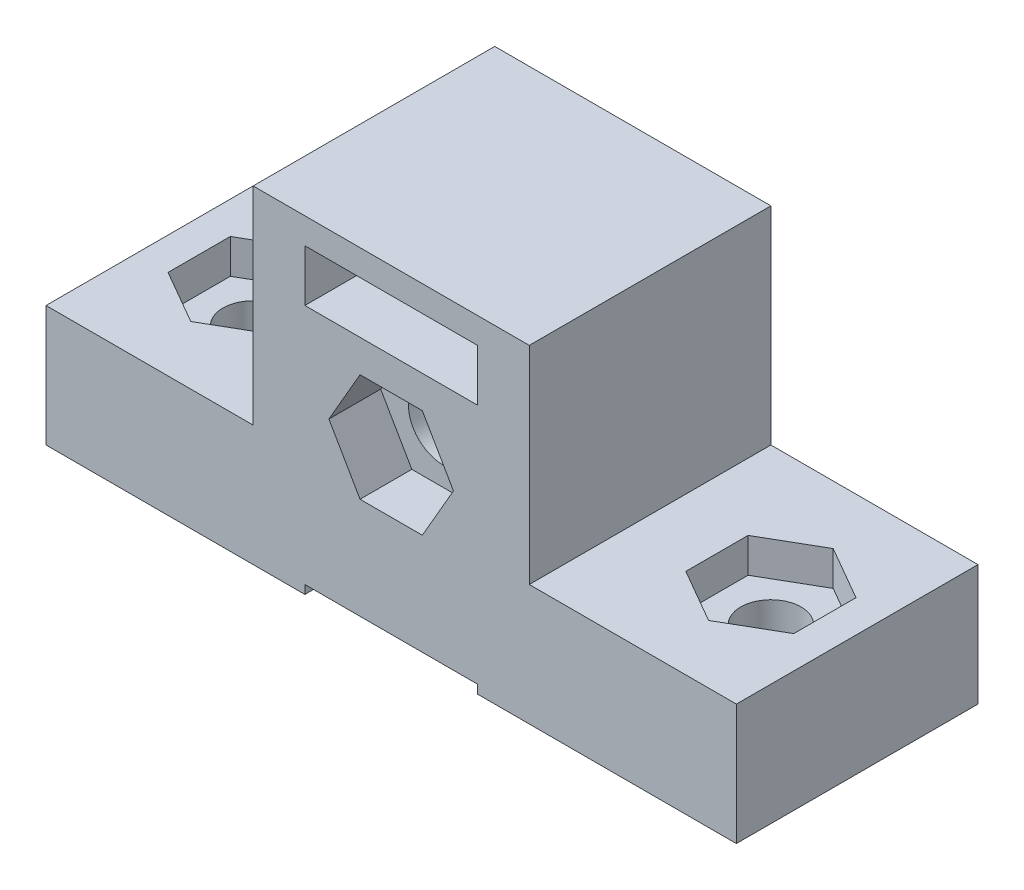
SolidWorks part; units mm, degrees
ref_plane "Front Plane" through (0, 0, 0) normal (0, 0, 1) x (1, 0, 0)
ref_plane "Top Plane" through (0, 0, 0) normal (0, 1, 0) x (1, 0, 0)
ref_plane "Right Plane" through (0, 0, 0) normal (1, 0, 0) x (0, 0, -1)
sketch "Sketch1" plane through (0, 0, 0) normal (0, 1, 0) x (1, 0, 0)
  line L1 (-20, 7) -> (20, 7)
  line L2 (-20, 7) -> (-20, -7)
  line L3 (-20, -7) -> (20, -7)
  line L4 (20, 7) -> (20, -7)
  line L5 (-20, 7) -> (20, -7) construction
  line L6 (-20, -7) -> (20, 7) construction
  point P0 (0, 0)
  dimension "D1" = 40
  dimension "D2" = 14
extrude "Boss-Extrude1" add sketch "Sketch1" along normal blind 19
sketch "Sketch2" plane through (0, 0, 7) normal (0, 0, 1) x (1, 0, 0)
  line L0 (0, 19) -> (0, 0) construction
  line L1 (-20, 19) -> (20, 19) construction
  line L3 (-5, 14.5) -> (5, 14.5)
  line L4 (-5, 14.5) -> (-5, 17.5)
  line L5 (-5, 17.5) -> (5, 17.5)
  line L6 (5, 14.5) -> (5, 17.5)
  line L7 (-5, 14.5) -> (5, 17.5) construction
  line L8 (-5, 17.5) -> (5, 14.5) construction
  line L9 (-5, -0.5) -> (5, -0.5)
  line L10 (-5, -0.5) -> (-5, 0.5)
  line L11 (-5, 0.5) -> (5, 0.5)
  line L12 (5, -0.5) -> (5, 0.5)
  line L13 (-5, -0.5) -> (5, 0.5) construction
  line L14 (-5, 0.5) -> (5, -0.5) construction
  point P5 (0, 16)
  dimension "D1" = 10
  dimension "D2" = 3
  dimension "D3" = 16
  dimension "D4" = 10
  dimension "D5" = 1
extrude "Cut-Extrude1" cut sketch "Sketch2" against normal blind 30
sketch "Sketch3" plane through (0, 0, 7) normal (0, 0, 1) x (1, 0, 0)
  line L0 (0, 19) -> (0, 0) construction
  line L1 (-20, 19) -> (20, 19) construction
  circle A0 centre (0, 9.5) radius 2
  dimension "D1" = 4
extrude "Cut-Extrude2" cut sketch "Sketch3" against normal through all
sketch "Sketch4" plane through (0, 19, 0) normal (0, 1, 0) x (1, 0, 0)
  line L0 (-20, 0) -> (20, 0) construction
  line L1 (-20, 7) -> (-20, -7) construction
  line L2 (20, -7) -> (20, 7) construction
  line L3 (0, 7) -> (0, -7) construction
  line L4 (20, 7) -> (-20, 7) construction
  line L5 (-20, -7) -> (20, -7) construction
  circle A0 centre (-15, 0) radius 1.75
  circle A1 centre (15, 0) radius 1.75
  dimension "D1" = 3.5
  dimension "D2" = 15
extrude "Cut-Extrude3" cut sketch "Sketch4" against normal through all
sketch "Sketch8" plane through (0, 0, 0) normal (0, -1, 0) x (-1, 0, 0)
  line L0 (-5, 7) -> (-5, -7) construction
  line L1 (5, -7) -> (-5, -7)
  line L2 (5, -7) -> (5, -6)
  line L3 (5, -6) -> (-5, -6)
  line L4 (-5, -7) -> (-5, -6)
  dimension "D1" = 1
extrude "Boss-Extrude2" [suppressed] add sketch "Sketch8" against normal up to next
sketch "Sketch9" plane through (0, 19, 0) normal (0, 1, 0) x (1, 0, 0)
  line L0 (0, 7) -> (0, -7) construction
  line L1 (-15, 3.6084) -> (-18.125, 1.8042)
  line L2 (-18.125, 1.8042) -> (-18.125, -1.8042)
  line L3 (-18.125, -1.8042) -> (-15, -3.6084)
  line L4 (-15, -3.6084) -> (-11.875, -1.8042)
  line L5 (-11.875, -1.8042) -> (-11.875, 1.8042)
  line L6 (-11.875, 1.8042) -> (-15, 3.6084)
  line L7 (20, 7) -> (-20, 7) construction
  line L8 (-20, -7) -> (20, -7) construction
  line L9 (11.875, 1.8042) -> (15, 3.6084)
  line L10 (11.875, -1.8042) -> (11.875, 1.8042)
  line L11 (15, -3.6084) -> (11.875, -1.8042)
  line L12 (18.125, -1.8042) -> (15, -3.6084)
  line L13 (18.125, 1.8042) -> (18.125, -1.8042)
  line L14 (15, 3.6084) -> (18.125, 1.8042)
  circle A0 centre (-15, 0) radius 3.125 construction
  circle A1 centre (15, 0) radius 3.125 construction
  dimension "D1" = 6.25
extrude "Cut-Extrude4" cut sketch "Sketch9" against normal offset from surface (14 mm away) 5 up to face at (15, 0, -1.75)
sketch "Sketch10" plane through (0, 0, 7) normal (0, 0, 1) x (1, 0, 0)
  line L1 (1.8042, 12.625) -> (-1.8042, 12.625)
  line L2 (-1.8042, 12.625) -> (-3.6084, 9.5)
  line L3 (-3.6084, 9.5) -> (-1.8042, 6.375)
  line L4 (-1.8042, 6.375) -> (1.8042, 6.375)
  line L5 (1.8042, 6.375) -> (3.6084, 9.5)
  line L6 (3.6084, 9.5) -> (1.8042, 12.625)
  circle A0 centre (0, 9.5) radius 3.125 construction
  dimension "D1" = 6.25
extrude "Cut-Extrude5" cut sketch "Sketch10" against normal blind 3
sketch "Sketch11" plane through (0, 0, 7) normal (0, 0, 1) x (1, 0, 0)
  line L0 (0, 19) -> (0, 0) construction
  line L1 (-20, 19) -> (-8, 19)
  line L2 (-20, 19) -> (-20, 7)
  line L3 (-20, 7) -> (-8, 7)
  line L4 (-8, 19) -> (-8, 7)
  line L5 (-20, 19) -> (20, 19) construction
  line L6 (-20, 0) -> (-5, 0) construction
  line L7 (8, 19) -> (8, 7)
  line L8 (20, 7) -> (8, 7)
  line L9 (20, 19) -> (20, 7)
  line L10 (20, 19) -> (8, 19)
  dimension "D1" = 8
  dimension "D2" = 7
extrude "Cut-Extrude6" cut sketch "Sketch11" against normal through all
equation "\"X-ROD-SPACING\"=45"
equation "\"Y-ROD-SPACING\"=75"
equation "\"Z-ROD-SPACING\"=17.5"
equation "\"Y-BED-OFFSET\"=2"
equation "\"Y-BED-ROD-INSET\"=3.5"
equation "\"Y-BED-SCREW-SPACING\"=209"
equation "\"Y-BED-SCREW-CUTOUT-SLOT-HEIGHT\"=2.5"
equation "\"T-SLOT-NUT-FILLET-RADIUS\"=0.5"
equation "\"T-SLOT-SCREW-SHAFT-RADIUS\"=1.55"
equation "\"T-SLOT-SCREW-SHAFT-CUTOUT-LENGTH\"=11"
equation "\"T-SLOT-NUT-DEPTH\"=3.5"
equation "\"T-SLOT-NUT-WIDTH\"=2.85"
equation "\"T-SLOT-NUT-END-DISTANCE\"=8"
equation "\"ACRYLIC-THICKNESS\"=10"
equation "\"ACRYLIC-THICKNESS2\"=4.5"
equation "\"ACRYLIC-TAB-CUTOUT-SIZE\"=\"ACRYLIC-THICKNESS\"+\"ACRYLIC-TAB-TOLERANCE\"*2"
equation "\"ACRYLIC-TAB-TOLERANCE\"=-.05"
equation "\"ACRYLIC-TAB-WIDTH\"=\"ACRYLIC-THICKNESS\""
equation "\"ACRYLIC-M3-HOLE\"=2.9"
equation "\"SMOOTHROD-CAP-SCREW-DISTANCE\"=20"
equation "\"FRAME-WIDTH-INNER\"=370"
equation "\"NEMA17-HOLE-SPACING\"=31"
equation "\"NEMA17-CENTRAL-CUTOUT\"=22.5"
equation "\"Z-BRACKET-REACH\"=57"
equation "\"Z-ROD-INSET\"=13.5"
equation "\"TOP-BRACKET-SPACING\"=40"
equation "\"SMOOTHROD-X-LENGTH\"=350"
equation "\"SMOOTHROD-Y-LENGTH\"=350"
equation "\"SMOOTHROD-Z-LENGTH\"=350"
equation "\"SMOOTHROD-TIGHTENING-HEADROOM\"=.25"
equation "\"LEADSCREW-Z-LENGTH\"=300"
equation "\"SCREW-LENGTH-FRAME\"=\"ACRYLIC-THICKNESS\" + 10"
equation "\"SCREW-LENGTH-MOTOR\"=\"ACRYLIC-THICKNESS\" + 5"
equation "\"SCREW-LENGTH-EXTRUDER\"=28"
equation "\"SCREW-HEAD-RADIUS\"=6"
equation "\"PRINTED-M3-HOLE\"=3.5"
equation "\"PRINTED-X-SMOOTHROD-DIAMETER\"=8.8"
equation "\"PRINTED-X-SMOOTHROD-CUTOUT\"=10"
equation "\"PRINTED-X-BASE-HEIGHT\"=10"
equation "\"PRINTED-LM8UU-CUTOUT-SIZE\"=15.5"
equation "\"PRINTED-LM8UU-CUTOUT-LENGTH\"=24.5"
equation "\"PRINTED-X-IDLER-HEIGHT\"=16"
equation "\"PSU-MOUNTING-WIDTH\"=50"
equation "\"PSU-MOUNTING-HEIGHT\"=150"
equation "\"Y-BELT-TO-ROD-DISTANCE\"=20"
equation "\"SPOOL-HOLDER-ROD-SPACING\"=150"
equation "\"ACRYLIC-X-CARRIAGE-WIDTH\"=55"
equation "\"ACRYLIC-X-CARRIAGE-HEIGHT\"=75"
equation "\"ACRYLIC-X-CARRIAGE-LM8UU-CUTOUT-WIDTH\"=24.25"
equation "\"ACRYLIC-X-CARRIAGE-LM8UU-CUTOUT-HEIGHT\"=11.0"
equation "\"ACRYLIC-X-CARRIAGE-SCREW-SPACING-X\"=15"
equation "\"ACRYLIC-X-CARRIAGE-SCREW-SPACING-Y\"=33"
equation "\"ACRYLIC-X-CARRIAGE-CENTER-TAB-SPACING\"=14"
equation "\"ACRYLIC-X-CARRIAGE-EXTRUDER-OFFSET\"=26"
equation "\"ACRYLIC-X-CARRIAGE-EXTRUDER-ANGLE\"=90"
equation "\"ACRYLIC-X-CARRIAGE-EXTRUDER-SHELF-DEPTH\"=\"ACRYLIC-X-CARRIAGE-EXTRUDER-OFFSET\" + 28"
equation "\"ACRYLIC-X-CARRIAGE-EXTRUDER-BRACE-SPACING\"=23"
equation "\"ACRYLIC-X-CARRIAGE-EXTRUDER-BRACE-TAB-OFFSET\"=20"
equation "\"ACRYLIC-X-CARRIAGE-EXTRUDER-BRACE-HEIGHT\"=35"
equation "\"ACRYLIC-X-CARRIAGE-EXTRUDER-BRACE-SCREW-SPACING\"=22"
equation "\"ACRYLIC-X-CARRIAGE-DUAL-WIDTH-MULTIPLIER\"=1.65"
equation "\"ACRYLIC-X-CARRIAGE-DUAL-HOTEND-SPACING\"=42"
equation "\"ACRYLIC-X-CARRIAGE-DUAL-WIDTH\"=75"
equation "\"ACRYLIC-X-CARRIAGE-DUAL-HOTEND-SEPARATION\"=36"
equation "\"ACRYLIC-X-CARRIAGE-DUAL-MOUNT-PLATE-DEPTH\"=75"
equation "\"ACRYLIC-X-CARRIAGE-DUAL-MOUNT-BRACE-WIDTH\"=33"
equation "\"ACRYLIC-X-CARRIAGE-DUAL-MOUNT-SCREW-WIDTH\"=40"
equation "\"BLOWER-FAN-WIDTH\"=15"
equation "\"PRINTED-M3-NUT-AF\"=6.25"
equation "\"D1@Sketch9\"=\"PRINTED-M3-NUT-AF\""
equation "\"D1@Sketch10\"=\"PRINTED-M3-NUT-AF\""
equation "\"D1@Sketch4\"=\"PRINTED-M3-HOLE\""
